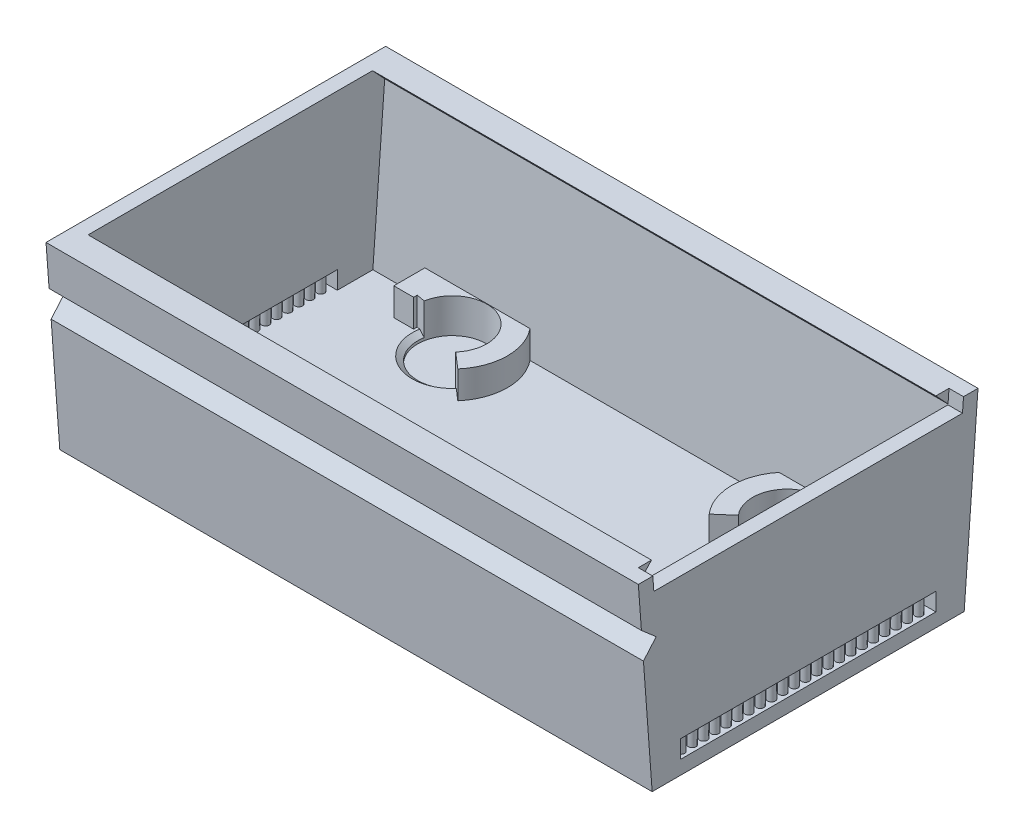
SolidWorks part; units mm, degrees
ref_plane "Plano frontal" through (0, 0, 0) normal (0, 0, 1) x (1, 0, 0)
ref_plane "Plano superior" through (0, 0, 0) normal (0, 1, 0) x (1, 0, 0)
ref_plane "Plano direito" through (0, 0, 0) normal (1, 0, 0) x (0, 0, -1)
sketch "Esboço1" plane through (0, 0, 0) normal (0, 1, 0) x (1, 0, 0)
  line L1 (0, 0) -> (83.7, 0)
  line L2 (0, 0) -> (0, -45.2)
  line L3 (0, -45.2) -> (83.7, -45.2)
  line L4 (83.7, 0) -> (83.7, -45.2)
  dimension "D1" = 83.7
  dimension "D2" = 45.2
extrude "Base" add sketch "Esboço1" along normal blind 2
sketch "Esboço10" plane through (0, 0, 0) normal (-1, 0, 0) x (0, 0, 1)
  line L0 (0, 0) -> (-2, 27)
  line L1 (-2, 27) -> (0.1, 27)
  line L2 (0.1, 27) -> (2.1, 0)
  line L3 (0, 0) -> (45.2, 0) construction
  line L4 (2.1, 0) -> (0, 0)
  line L5 (22.6, 0) -> (22.6, 38.9101) construction
  line L6 (43.1, 0) -> (45.2, 0)
  line L7 (45.1, 27) -> (43.1, 0)
  line L8 (47.2, 27) -> (45.1, 27)
  line L9 (45.2, 0) -> (47.2, 27)
  point P3 (-0.95, 27)
  dimension "D1" = 2.1
  dimension "D2" = 27
  dimension "D3" = 2
extrude "Paredes Laterais" add sketch "Esboço10" against normal through all
sketch "Esboço12" plane through (0, 0, 0) normal (-1, 0, 0) x (0, 0, 1)
  line L0 (45.2, 0) -> (0, 0)
  line L1 (0, 0) -> (-2, 27)
  line L2 (-2, 27) -> (47.2, 27)
  line L3 (47.2, 27) -> (45.2, 0)
extrude "Parede Corpo" add sketch "Esboço12" along normal blind 2.1
sketch "Esboço13" plane through (83.7, 0, 0) normal (1, 0, 0) x (0, 0, -1)
  line L0 (-47.0519, 25) -> (1.8519, 25)
  line L1 (-45.2, 0) -> (-47.2, 27) construction
  line L2 (2, 27) -> (0, 0) construction
  line L3 (1.8519, 25) -> (0, 0)
  line L4 (0, 0) -> (-45.2, 0)
  line L5 (-45.2, 0) -> (-47.0519, 25)
  line L6 (-47.2, 27) -> (-45.1, 27) construction
  point P12 (-46.15, 27)
  dimension "D1" = 2
extrude "Parede Cabeça" add sketch "Esboço13" against normal blind 2.1
sketch "Esboço14" plane through (83.7, 0, 0) normal (1, 0, 0) x (0, 0, -1)
  line L0 (-46.9037, 23) -> (-43.2, 27)
  line L1 (-45.2, 0) -> (-47.2, 27) construction
  line L2 (-45.1, 27) -> (-0.1, 27) construction
  line L3 (-43.2, 27) -> (-47.2, 27)
  line L4 (-47.2, 27) -> (-46.9037, 23)
  line L5 (-22.6, 25) -> (-22.6, -2.7802) construction
  line L6 (-0.2481, 25) -> (-44.9519, 25) construction
  line L7 (2, 27) -> (1.7037, 23)
  line L8 (-2, 27) -> (2, 27)
  line L9 (1.7037, 23) -> (-2, 27)
  dimension "D1" = 4
  dimension "D2" = 4
extrude "Trilho Tampa" add sketch "Esboço14" against normal blind 81.6 from offset 2.1 offset against normal yes
sketch "Esboço15" plane through (83.7, 0, 0) normal (1, 0, 0) x (0, 0, -1)
  line L0 (-46.9037, 23) -> (-43.2, 19.2634)
  line L1 (-45.2, 0) -> (-47.2, 27) construction
  line L2 (-43.2, 19.2634) -> (-46.3127, 15.0219)
  line L3 (-46.3127, 15.0219) -> (-46.9037, 23)
  dimension "D1" = 8
  dimension "D2" = 4
extrude "Trilho Core" add sketch "Esboço15" against normal through all
sketch "Esboço18" plane through (83.7, 0, 0) normal (1, 0, 0) x (0, 0, -1)
  line L0 (-46.7556, 21) -> (-44.6133, 19.1532)
  line L1 (-45.2, 0) -> (-47.2, 27) construction
  line L2 (-44.6133, 19.1532) -> (-46.4601, 17.0109)
  line L3 (-46.4601, 17.0109) -> (-46.7556, 21)
  dimension "D1" = 6
  dimension "D2" = 4
  dimension "D3" = 2
extrude "Corte Trilho core" cut sketch "Esboço18" against normal through all
sketch "Esboço19" plane through (83.7, 0, 0) normal (1, 0, 0) x (0, 0, -1)
  line L0 (-41.1, 4.59) -> (-41.1, 2)
  line L1 (-41.1, 2) -> (-4.1, 2)
  line L2 (-4.1, 2) -> (-4.1, 4.59)
  line L3 (-4.1, 4.59) -> (-41.1, 4.59)
  line L4 (-45.2, 0) -> (0, 0) construction
  dimension "D1" = 37
  dimension "D2" = 4.1
  dimension "D3" = 2
  dimension "D4" = 2.59
extrude "Corte - Conector Cabeça" cut sketch "Esboço19" against normal blind 2.1
sketch "Esboço20" plane through (-2.1, 0, 0) normal (-1, 0, 0) x (0, 0, 1)
  line L0 (7.1, 4.59) -> (7.1, 2)
  line L1 (7.1, 2) -> (38.1, 2)
  line L2 (38.1, 2) -> (38.1, 4.59)
  line L3 (38.1, 4.59) -> (7.1, 4.59)
  line L4 (0, 0) -> (45.2, 0) construction
  dimension "D1" = 31
  dimension "D2" = 2.59
  dimension "D3" = 2
  dimension "D4" = 7.1
extrude "Corte-Conector Corpo" cut sketch "Esboço20" against normal blind 2.1
sketch "Esboço21" plane through (0, 2, 0) normal (0, 1, 0) x (1, 0, 0)
  line L0 (71.2, -2) -> (71.2, -4.4519)
  line L1 (0, -2) -> (81.6, -2) construction
  line L2 (71.2, -4.4519) -> (75.2, -4.4519)
  line L3 (75.2, -4.4519) -> (75.2, -1.9519)
  line L4 (0, -1.9519) -> (81.6, -1.9519) construction
  line L5 (75.2, -1.9519) -> (71.2, -2)
  line L6 (83.7, -0.2481) -> (83.7, -44.9519) construction
  line L8 (-2.1, -22.6) -> (100.2362, -22.6) construction
  line L9 (-2.1, -47.2) -> (-2.1, 2) construction
  line L10 (75.2, -43.2481) -> (71.2, -43.2)
  line L11 (75.2, -40.7481) -> (75.2, -43.2481)
  line L12 (71.2, -40.7481) -> (75.2, -40.7481)
  line L13 (71.2, -43.2) -> (71.2, -40.7481)
  line L14 (81.6, -43.2481) -> (0, -43.2481) construction
  line L15 (6.4, -1.9519) -> (10.4, -1.9519)
  line L16 (6.4, -1.9519) -> (6.4, -6.4519)
  line L17 (6.4, -6.4519) -> (10.4, -6.4519)
  line L18 (10.4, -1.9519) -> (10.4, -6.4519)
  line L19 (6.4, -43.2481) -> (10.4, -43.2481)
  line L20 (6.4, -43.2481) -> (6.4, -38.7481)
  line L21 (6.4, -38.7481) -> (10.4, -38.7481)
  line L22 (10.4, -43.2481) -> (10.4, -38.7481)
  dimension "D1" = 8.5
  dimension "D2" = 4
  dimension "D3" = 2.5
  dimension "D4" = 4
  dimension "D5" = 4
  dimension "D6" = 8.5
  dimension "D7" = 8.5
  dimension "D8" = 4.5
  dimension "D9" = 4.5
extrude "Apoio Conector Cabeça" add sketch "Esboço21" along normal blind 4
sketch "Esboço22" plane through (0, 2, 0) normal (0, 1, 0) x (1, 0, 0)
  line L0 (83.7, -0.2481) -> (83.7, -44.9519) construction
  line L1 (0, -2) -> (81.6, -2) construction
  line L4 (40.8, -47.2) -> (40.8, 6.2716) construction
  line L5 (83.7, -47.2) -> (-2.1, -47.2) construction
  circle A0 centre (65.05, -7) radius 5
  circle A1 centre (16.55, -7) radius 5
  dimension "D2" = 10
  dimension "D1" = 18.65
  dimension "D4" = 5
extrude "Corte-imã" cut sketch "Esboço22" against normal blind 1
sketch "Esboço24" plane through (0, 2, 0) normal (0, 1, 0) x (1, 0, 0)
  line L0 (83.7, -0.2481) -> (83.7, -44.9519) construction
  line L1 (16.55, -7) -> (22.5925, -12.2429)
  line L2 (10.4, -1.9519) -> (75.2, -1.9519) construction
  line L3 (40.8, -2) -> (40.8, 12.7863) construction
  line L4 (0, -2) -> (81.6, -2) construction
  line L5 (-2.1, -47.2) -> (-2.1, 2) construction
  line L7 (16.55, -7) -> (8.669, -5.6254)
  line L8 (65.05, -7) -> (72.1038, -3.2259)
  line L9 (65.05, -7) -> (59.0075, -12.2429)
  circle A0 centre (16.55, -7) radius 8
  circle A1 centre (65.05, -7) radius 8
  point P5 (6.2, -4.4519)
  point P13 (8.669, -5.6254)
  point P14 (72.1038, -3.2259)
  dimension "D1" = 16
  dimension "D2" = 10.291
  dimension "D3" = 11.5962
  dimension "D4" = 10.769
extrude "Ressalto-extrusão15" add sketch "Esboço24" along normal blind 4
sketch "Esboço25" plane through (0, 2, 0) normal (0, 1, 0) x (1, 0, 0)
  line L0 (83.7, -0.2481) -> (83.7, -44.9519) construction
  line L1 (81.6, -4.1) -> (83.7, -4.1) construction
  circle A0 centre (82.7, -5.6) radius 0.55
  circle A1 centre (82.7, -7.24) radius 0.55
  circle A2 centre (82.7, -8.88) radius 0.55
  circle A3 centre (82.7, -10.52) radius 0.55
  circle A4 centre (82.7, -12.16) radius 0.55
  circle A5 centre (82.7, -13.8) radius 0.55
  circle A6 centre (82.7, -15.44) radius 0.55
  circle A7 centre (82.7, -17.08) radius 0.55
  circle A8 centre (82.7, -18.72) radius 0.55
  circle A9 centre (82.7, -20.36) radius 0.55
  circle A10 centre (82.7, -22) radius 0.55
  circle A11 centre (82.7, -23.64) radius 0.55
  circle A12 centre (82.7, -25.28) radius 0.55
  circle A13 centre (82.7, -26.92) radius 0.55
  circle A14 centre (82.7, -28.56) radius 0.55
  circle A15 centre (82.7, -30.2) radius 0.55
  circle A16 centre (82.7, -31.84) radius 0.55
  circle A17 centre (82.7, -33.48) radius 0.55
  circle A18 centre (82.7, -35.12) radius 0.55
  circle A19 centre (82.7, -36.76) radius 0.55
  circle A20 centre (82.7, -38.4) radius 0.55
  circle A21 centre (82.7, -40.04) radius 0.55
  dimension "D1" = 1.1
  dimension "D2" = 1
  dimension "D3" = 1.5
  dimension "D4" = 22
chamfer "Chanfro7" distance 0.8 angle 37 2 edges at (14.4037, 2, 11.5159) (67.8855, 2, 11.1183)
extrude "Ressalto-extrusão16" add sketch "Esboço25" along normal blind 2.6
sketch "Esboço27" plane through (0, 2, 0) normal (0, 1, 0) x (1, 0, 0)
  line L0 (-2.1, -47.2) -> (-2.1, 2) construction
  line L1 (0, -7.1) -> (-2.1, -7.1) construction
  circle A0 centre (-1.1, -8.4) radius 0.55
  circle A1 centre (-1.1, -10) radius 0.55
  circle A2 centre (-1.1, -11.6) radius 0.55
  circle A3 centre (-1.1, -13.2) radius 0.55
  circle A4 centre (-1.1, -14.8) radius 0.55
  circle A5 centre (-1.1, -16.4) radius 0.55
  circle A6 centre (-1.1, -18) radius 0.55
  circle A7 centre (-1.1, -19.6) radius 0.55
  circle A8 centre (-1.1, -21.2) radius 0.55
  circle A9 centre (-1.1, -22.8) radius 0.55
  circle A10 centre (-1.1, -24.4) radius 0.55
  circle A11 centre (-1.1, -26) radius 0.55
  circle A12 centre (-1.1, -27.6) radius 0.55
  circle A13 centre (-1.1, -29.2) radius 0.55
  circle A14 centre (-1.1, -30.8) radius 0.55
  circle A15 centre (-1.1, -32.4) radius 0.55
  circle A16 centre (-1.1, -34) radius 0.55
  circle A17 centre (-1.1, -35.6) radius 0.55
  circle A18 centre (-1.1, -37.2) radius 0.55
  dimension "D1" = 1.1
  dimension "D2" = 1
  dimension "D3" = 1.3
  dimension "D4" = 19
extrude "Ressalto-extrusão17" add sketch "Esboço27" along normal blind 2.6
chamfer "Chanfro5" distance 1 angle 37 4 edges at (75.2, 4, 40.7481) (75.2, 6, 41.9981) (75.2, 6, 3.2019) (75.2, 4, 4.4519)
chamfer "Chanfro6" distance 1.5 angle 37 4 edges at (6.4, 6, 4.2019) (6.4, 4, 6.4519) (6.4, 6, 40.9981) (6.4, 4, 38.7481)
